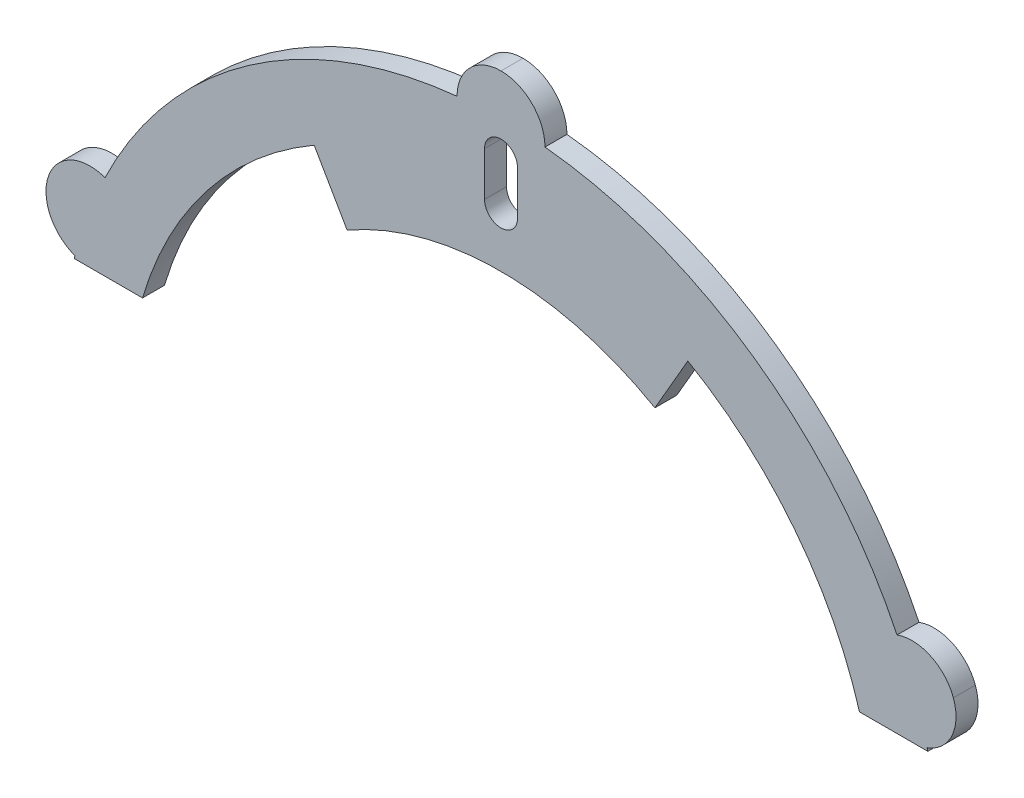
SolidWorks part; units mm, degrees
ref_plane "Front Plane" through (0, 0, 0) normal (0, 0, 1) x (1, 0, 0)
ref_plane "Top Plane" through (0, 0, 0) normal (0, 1, 0) x (1, 0, 0)
ref_plane "Right Plane" through (0, 0, 0) normal (1, 0, 0) x (0, 0, -1)
sketch "Sketch1" plane through (0, 0, 0) normal (0, 0, 1) x (1, 0, 0)
  line L0 (0, 134.1427) -> (0, -152.556) construction
  line L2 (-148.9091, 0) -> (221.1932, 0) construction
  line L3 (0, 0) -> (-119.341, 43.4366) construction
  line L5 (-12.7, 126.3634) -> (-12.7, 139.0634)
  line L6 (-12.7, 139.0634) -> (12.7, 139.0634)
  line L7 (12.7, 126.3634) -> (12.7, 139.0634)
  line L8 (-20.0381, 107.9663) -> (12.7, 139.0634) construction
  line L9 (-12.7, 139.0634) -> (20.0381, 107.9663) construction
  line L10 (-119.341, 43.4366) -> (-153.5642, 55.8928) construction
  line L11 (-135.0205, 35.6284) -> (-126.3332, 59.4966)
  line L12 (-126.3332, 59.4966) -> (-114.3991, 55.1529)
  line L13 (-135.0205, 35.6284) -> (-123.0864, 31.2847)
  line L14 (126.3332, 59.4966) -> (114.3991, 55.1529)
  line L15 (135.0205, 35.6284) -> (126.3332, 59.4966)
  line L16 (135.0205, 35.6284) -> (123.0864, 31.2847)
  line L18 (0, 0) -> (-82.628, 143.1159) construction
  line L19 (-44.45, 76.9897) -> (-53.975, 93.4874)
  line L20 (44.45, 76.9897) -> (53.975, 93.4874)
  line L21 (-123.2882, 30.48) -> (-103.5576, 30.48)
  line L22 (103.5576, 30.48) -> (123.2882, 30.48)
  arc A0 (-123.0864, 31.2847) -> (-123.2882, 30.48) centre (0, 0) ccw
  arc A1 (44.45, 76.9897) -> (-44.45, 76.9897) centre (0, 0) ccw
  arc A2 (-12.7, 126.3634) -> (-114.3991, 55.1529) centre (0, 0) ccw
  arc A3 (114.3991, 55.1529) -> (12.7, 126.3634) centre (0, 0) ccw
  arc A4 (123.2882, 30.48) -> (123.0864, 31.2847) centre (0, 0) ccw
  arc A5 (103.5576, 30.48) -> (53.975, 93.4874) centre (0, 0) ccw
  arc A6 (-53.975, 93.4874) -> (-103.5576, 30.48) centre (0, 0) ccw
  point P10 (0, 127)
  point P22 (-130.6769, 47.5625)
  dimension "D1" = 254
  dimension "D2" = 177.8
  dimension "D10" = 215.9
  dimension "D3" = 20
  dimension "D4" = 12.7
  dimension "D5" = 12.7
  dimension "D6" = 25.4
  dimension "D7" = 12.7
  dimension "D8" = 25.4
  dimension "D9" = 30
  dimension "D11" = 30.48
extrude "Boss-Extrude1" add sketch "Sketch1" along normal blind 6.35
fillet "Fillet1" radius 12.7 6 edges at (135.0205, 35.6284, 3.175) (126.3332, 59.4966, 3.175) (-135.0205, 35.6284, 3.175) (-126.3332, 59.4966, 3.175) (-12.7, 139.0634, 3.175) (12.7, 139.0634, 3.175)
sketch "Sketch2" plane through (0, 0, 6.35) normal (0, 0, 1) x (1, 0, 0)
  line L0 (0, 158.3353) -> (0, -13.4156) construction
  line L1 (-143.9955, 0) -> (139.073, 0) construction
  line L4 (-4.7625, 104.5419) -> (-4.7625, 117.2419)
  line L6 (4.7625, 104.5375) -> (4.7625, 117.2375)
  line L7 (-4.7625, 104.5419) -> (4.7625, 117.2375) construction
  line L8 (-4.7625, 117.2419) -> (4.7625, 104.5375) construction
  arc A0 (4.7625, 117.2375) -> (-4.7625, 117.2419) centre (0, 117.2375) ccw
  arc A1 (-4.7625, 104.5419) -> (4.7625, 104.5375) centre (0, 104.5375) ccw
  point P7 (0, 110.8897)
  point P15 (0.0022, 122)
  dimension "D1" = 4.7625
  dimension "D2" = 12.7
  dimension "D3" = 122
extrude "Cut-Extrude1" cut sketch "Sketch2" against normal through all both and the other way through all
equation "\"Wheel Thickness\"= 1in"
equation "\"Wheel Diameter\"= 3in"
equation "\"Motor Rear Diameter\" = 36.2mm"
equation "\"Motor Front Diameter\" = 12mm"
equation "\"Material Thickness\" = .25in"
equation "\"Wheel Cutout Diameter\"= 2cm"
equation "\"Motor Mount Tab Thickness\" = 100mm"
equation "\"Motor Mount Tab Height\" = 40mm"
equation "\"Motor Shaft Diameter\" = 3mm"
equation "\"Wheel Radius Clearance\" = 5mm"
equation "\"Wheel Cutout Width\" = 1.5in"
equation "\"Base Diameter\" = 10in"
equation "\"Wheel Mount Distance\" = 5mm"
equation "\"Motor Mount Distance\" = 50mm"
equation "\"Motor Cutout Length\" = 6in"
equation "\"Motor Cutout Height\" = 2in "
equation "\"Rod Diameter\" = 3/8in"
equation "\"Rod Length\" = 1.5in"
equation "\"Barrel Front Length\" = 1.8in"
equation "\"Barrerl Rear Length\" = 5in "
equation "\"Barrel Fillet Radius\" = 1in "
equation "\"Barrel Angle\" = 20deg"
equation "\"Barrel Diameter\" = 50mm"
equation "\"Barrel Shell Width\" = 2mm"
equation "\"Second Level Diameter\" = 10in"
equation "\"Ball Diameter\" = 40mm"
equation "\"Third Level Length\" = 9in"
equation "\"Third Level Height\" = 9in"
equation "\"Barrel Tab Clearance\" = 5mm"
equation "\"Barrel Tab Distance Away\" = 2mm"
equation "\"Hole Distance Apart\" = 2.8in"
equation "\"Barrel Tab Distance\"= 1.5in "
equation "\"Third Level Rod Distance\" = .5in"
equation " \"Second Rod Diameter\" = 3/8in"
equation "\"Second Rod Length\" = 3.88in"
equation "\"D1@Sketch1\"=\"Base Diameter\""
equation "\"D2@Sketch1\"=\"Base Diameter\"-3in"
equation "\"D1@Boss-Extrude1\"=\"Material Thickness\""
equation "\"D1@Sketch2\"=\"Rod Diameter\"/2"
equation "\"D3@Sketch2\"=(\"Base Diameter\"/2)-5mm"
equation "\"D10@Sketch1\"=\"Base Diameter\"-1.5"
equation "\"Bumper Wheel Clearance\" = 1.2in"
equation "\"D11@Sketch1\"=\"Bumper Wheel Clearance\""
